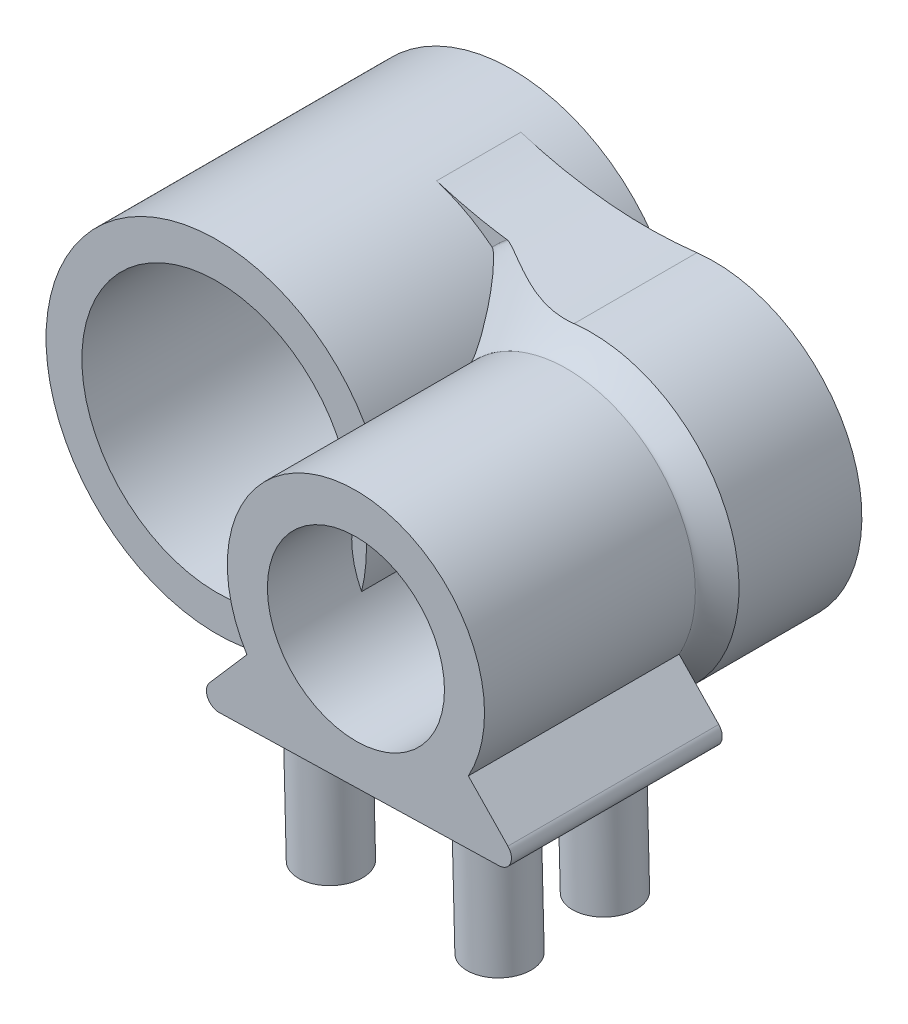
SolidWorks part; units mm, degrees
ref_plane "Front Plane" through (0, 0, 0) normal (0, 0, 1) x (1, 0, 0)
ref_plane "Top Plane" through (0, 0, 0) normal (0, 1, 0) x (1, 0, 0)
ref_plane "Right Plane" through (0, 0, 0) normal (1, 0, 0) x (0, 0, -1)
sketch "Sketch2" plane through (0, 0, 0) normal (0, 0, 1) x (1, 0, 0)
  circle A0 centre (0, 0) radius 3.2
  circle A3 centre (0, 0) radius 4.05
  dimension "D2" = 6.4
  dimension "D1" = 8.1
extrude "Boss-Extrude1" add sketch "Sketch2" along normal blind 7
sketch "Sketch3" plane through (0, 0, 7) normal (0, 0, 1) x (1, 0, 0)
  circle A0 centre (5.8, 0) radius 2.1
  circle A3 centre (0, 0) radius 4.05 construction
  circle A4 centre (5.8, 0) radius 3.05
  arc A5 (3.5121, -2.0169) -> (3.5121, 2.0169) centre (0, 0) ccw
  dimension "D1" = 4.2
  dimension "D2" = 6.1
  dimension "D3" = 5.8
extrude "Boss-Extrude2" add sketch "Sketch3" against normal blind 4 contours A0 region at (6.3146, 2.1195, 7)
extrude "Boss-Extrude4" add sketch "Sketch3<3>" along normal blind 2.5 separate body contours A0 | A0 region at (6.3146, 2.1195, 7) region at (3.3513, 0, 7)
sketch "Sketch3<3>" plane through (0, 0, 7) normal (0, 0, 1) x (1, 0, 0) same geometry as "Sketch3"
sketch "Sketch4" plane through (0, 0, 3) normal (0, 0, -1) x (-1, 0, 0)
  line L0 (-5.8, 0) -> (-8.2749, -2.4749)
  line L1 (0, 0) -> (-10.4842, 0) construction
  circle A0 centre (-5.8, 0) radius 3.5
  circle A1 centre (-5.8, 0) radius 2.5
  circle A2 centre (0, 0) radius 4.05 construction
  arc A3 (-3.258, 2.4058) -> (-3.258, -2.4058) centre (0, 0) ccw
  arc M1 (-3.9338, 0.963) -> (-3.5121, 2.0169) centre (0, 0) cw
  arc M2 (-3.5121, 2.0169) -> (-3.5121, -2.0169) centre (-5.8, 0) ccw
  dimension "D1" = 5
  dimension "D2" = 7
  dimension "D3" = 45
extrude "Boss-Extrude5" add sketch "Sketch4" along normal blind 2 contours L1 A3 A0 M2 | L1 A1 M1 M2 | L1 A0 L0 M2 | A1 L1 L0 M2 region at (8.3066, -1.0382, 3) region at (8.575, 0.0615, 3) region at (8.7532, -1.2232, 3) region at (9.075, 0.0698, 3)
sketch "Sketch5" plane through (0, 0, 9.5) normal (0, 0, 1) x (1, 0, 0)
  line L0 (5.8789, -3.049) -> (0.0828, -3.1989)
  line L1 (5.8789, -3.049) -> (9.8775, -2.9455)
  line L2 (5.8401, -1.5495) -> (9.8387, -1.446)
  line L3 (5.8401, -1.5495) -> (0.044, -1.6994)
  line L4 (3.2142, -1.6174) -> (1.8802, -3.1524)
  line L5 (8.466, -1.4815) -> (9.8775, -2.9455)
  circle A0 centre (5.8, 0) radius 3.05 construction
  circle A1 centre (5.8, 0) radius 3.05
  circle A2 centre (0, 0) radius 3.2 construction
  circle A3 centre (0, 0) radius 3.2
  point P15 (0, 0)
  point P16 (0, 0)
  point P19 (7.0952, -3.3338)
  circle M5 centre (5.8, 0) radius 3.05
  dimension "D2" = 4
  dimension "D3" = 4
  dimension "D1" = 1.5
extrude "Boss-Extrude6" add sketch "Sketch5" against normal blind 2.5 contours L4 L0 M5 region at (3.3518, -2.6555, 9.5)
extrude "Boss-Extrude7" add sketch "Sketch5<3>" against normal blind 5 contours L5 L1 M5 region at (8.3822, -2.5254, 9.5)
sketch "Sketch5<3>" plane through (0, 0, 9.5) normal (0, 0, 1) x (1, 0, 0) same geometry as "Sketch5"
sketch "Sketch6" plane through (0.0828, -3.1989, 0) normal (0.0259, -0.9997, 0) x (-0.9997, -0.0259, 0)
  line L0 (-9.7981, -9.5) -> (-1.7981, -9.5) construction
  line L1 (-1.7981, -7) -> (-1.7981, -9.5) construction
  line L2 (-9.7981, -4.5) -> (-9.7981, -9.5) construction
  line L3 (-5.7981, -4.5) -> (-9.7981, -4.5) construction
  circle A0 centre (-3.7981, -8.25) radius 0.75
  circle A1 centre (-7.7981, -8.25) radius 0.75
  circle A2 centre (-7.7981, -5.75) radius 0.75
  point P14 (0, 0)
  point P15 (0, 0)
  point P16 (0, 0)
  dimension "D1" = 1.25
  dimension "D5" = 1.5
  dimension "D2" = 2
  dimension "D3" = 2
  dimension "D4" = 1.25
extrude "Boss-Extrude8" add sketch "Sketch6" along normal blind 3 contours A0 | A1 | A2
fillet "Fillet2" [suppressed] radius 1
fillet "Fillet3" radius 0.3 2 edges at (1.8802, -3.1524, 8.25) (9.8775, -2.9455, 7)
extrude "Cut-Extrude1" cut sketch "Sketch3<5>" against normal blind 7 from offset 2 contours A0 A5 region at (3.8862, 0, 7) offset against normal yes
sketch "Sketch3<5>" plane through (0, 0, 7) normal (0, 0, 1) x (1, 0, 0) same geometry as "Sketch3"
extrude "Boss-Extrude10" add sketch "Sketch3<6>" along normal blind 0.5 contours A0 A5 region at (3.8862, 0, 7)
sketch "Sketch3<6>" plane through (0, 0, 7) normal (0, 0, 1) x (1, 0, 0) same geometry as "Sketch3"
fillet "Fillet4" radius 0.2 1 edges at (7.4222, 1.9023, 3) conic radius 0.2
fillet "Fillet6" radius 10 1 edges at (3.258, 2.4058, 2) conic radius 10
fillet "Fillet7" radius 1.5 1 edges at (3.5121, -2.0169, 5) conic radius 10
fillet "Fillet8" radius 1.5 1 edges at (7.8878, 2.2234, 3) conic radius 10
